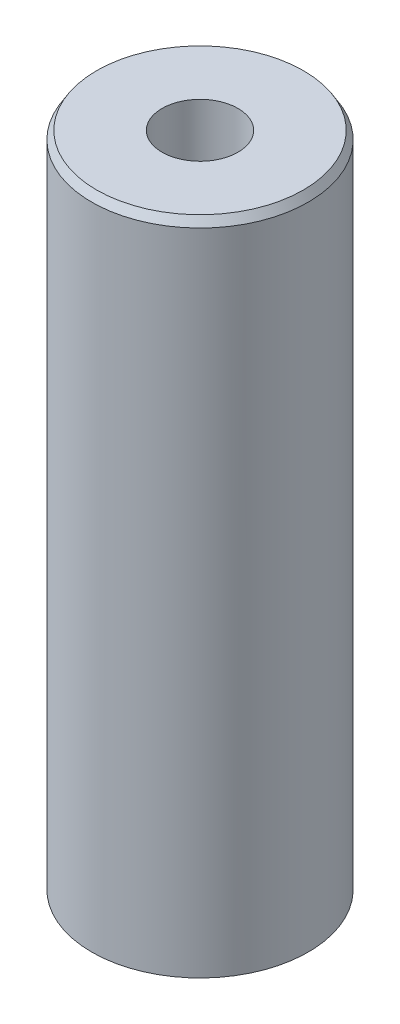
SolidWorks part; units mm, degrees
ref_plane "Front Plane" through (0, 0, 0) normal (0, 0, 1) x (1, 0, 0)
ref_plane "Top Plane" through (0, 0, 0) normal (0, 1, 0) x (1, 0, 0)
ref_plane "Right Plane" through (0, 0, 0) normal (1, 0, 0) x (0, 0, -1)
sketch "Sketch1" plane through (0, 0, 0) normal (0, 1, 0) x (1, 0, 0)
  circle A0 centre (0, 0) radius 5
  dimension "SHAFT_OD" = 10
extrude "Boss-Extrude1" add sketch "Sketch1" along normal blind 30.5851
sketch "Sketch2" plane through (0, 0, 0) normal (0, 1, 0) x (1, 0, 0)
  circle A0 centre (0, 0) radius 1.7534
  dimension "BORE_D" = 3.5067
extrude "Cut-Extrude1" cut sketch "Sketch2" along normal through all
chamfer "Chamfer1" distance 0.3732 angle 31.189 2 edges at (0, 30.5851, 5) (0, 0, 5) first distance on face at (0, 30.5851, 5) first distance on face at (0, 0, 1.7534)
